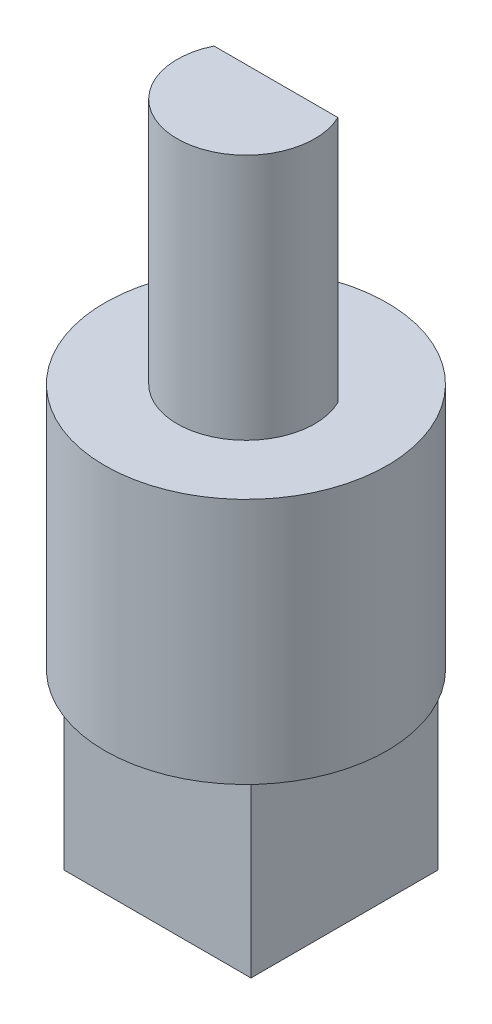
SolidWorks part; units mm, degrees
ref_plane "Front Plane" through (0, 0, 0) normal (0, 0, 1) x (1, 0, 0)
ref_plane "Top Plane" through (0, 0, 0) normal (0, 1, 0) x (1, 0, 0)
ref_plane "Right Plane" through (0, 0, 0) normal (1, 0, 0) x (0, 0, -1)
sketch "Sketch1" plane through (0, 0, 0) normal (0, 1, 0) x (1, 0, 0)
  line L7 (2.65, -2.5069) -> (-2.65, -2.5069)
  line L8 (2.65, -2.5069) -> (2.65, 2.7931)
  line L9 (2.65, 2.7931) -> (-2.65, 2.7931)
  line L10 (-2.65, -2.5069) -> (-2.65, 2.7931)
  line L11 (2.65, -2.5069) -> (-2.65, 2.7931) construction
  line L12 (2.65, 2.7931) -> (-2.65, -2.5069) construction
  point P0 (0, 0)
  dimension "D1" = 5.3
  dimension "D4" = 90
extrude "Boss-Extrude1" add sketch "Sketch1" along normal blind 5
sketch "Sketch2" plane through (0, 5, 0) normal (0, 1, 0) x (1, 0, 0)
  circle A1 centre (0, 0) radius 4
  dimension "D1" = 8
extrude "Boss-Extrude2" add sketch "Sketch2" along normal blind 7
sketch "Sketch3" plane through (0, 12, 0) normal (0, 1, 0) x (1, 0, 0)
  circle A0 centre (0, 0) radius 1.95
  dimension "D1" = 3.9
extrude "Boss-Extrude3" add sketch "Sketch3" along normal blind 7
sketch "Sketch4" plane through (0, 19, 0) normal (0, 1, 0) x (1, 0, 0)
  line L0 (0, -1.95) -> (0, 0.85) construction
  line L1 (0, 0.85) -> (1.755, 0.85) construction
  line L2 (0, 0.85) -> (-1.755, 0.85) construction
  line L3 (-1.755, 0.85) -> (1.755, 0.85)
  circle A0 centre (0, 0) radius 1.95 construction
  circle A1 centre (0, 0) radius 1.95 construction
  arc A2 (-1.755, 0.85) -> (1.755, 0.85) centre (0, 0) cw
  dimension "D1" = 2.8
extrude "Cut-Extrude1" cut sketch "Sketch4" against normal blind 7
